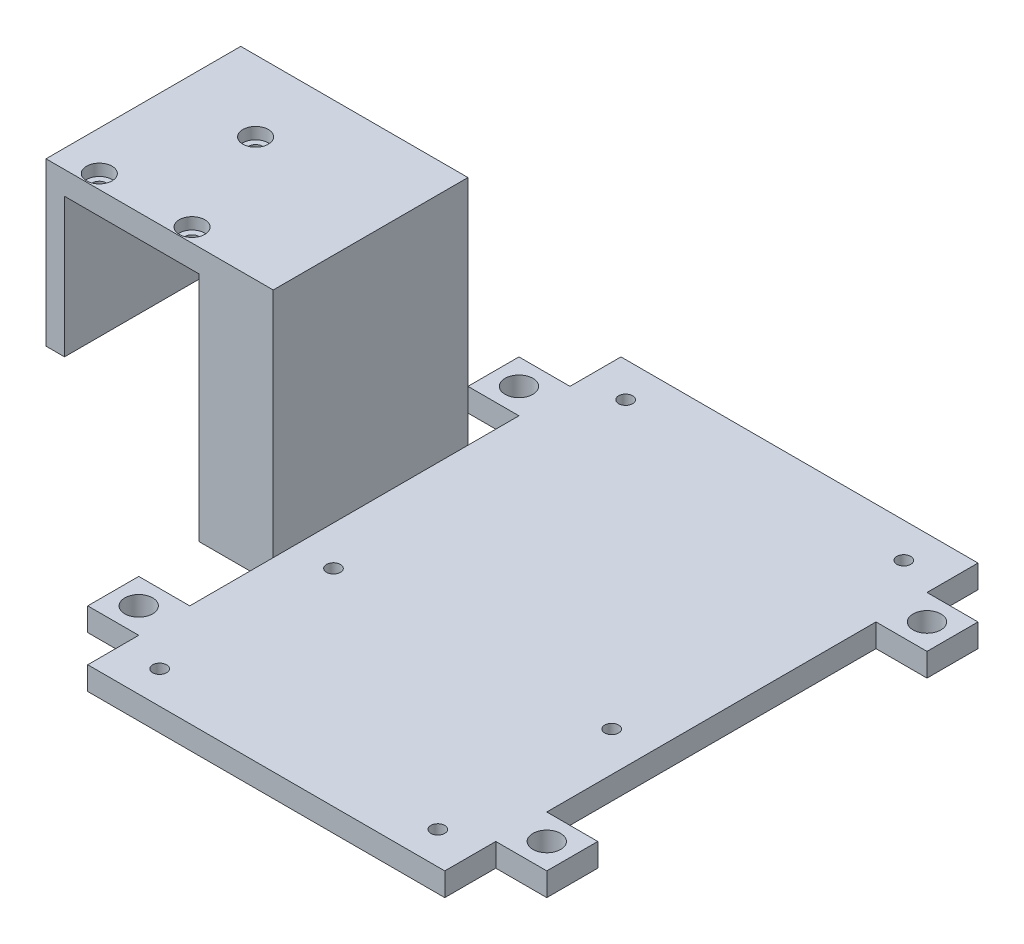
SolidWorks part; units mm, degrees
ref_plane "前视基准面" through (0, 0, 0) normal (0, 0, 1) x (1, 0, 0)
ref_plane "上视基准面" through (0, 0, 0) normal (0, 1, 0) x (1, 0, 0)
ref_plane "右视基准面" through (0, 0, 0) normal (1, 0, 0) x (0, 0, -1)
other "Configuration Table"
sketch "草图1" plane through (0, 0, 0) normal (0, 1, 0) x (1, 0, 0)
  line L1 (-14.5, 42) -> (14.5, 42)
  line L2 (-14.5, 42) -> (-14.5, 0)
  line L3 (-14.5, 0) -> (14.5, 0)
  line L4 (14.5, 42) -> (14.5, 0)
  line L6 (-14.5, 42) -> (-18.5, 42)
  line L7 (-14.5, 42) -> (-14.5, 0)
  line L8 (-14.5, 0) -> (-18.5, 0)
  line L9 (-18.5, 42) -> (-18.5, 0)
  line L10 (14.5, 42) -> (34.5, 42)
  line L11 (14.5, 42) -> (14.5, 0)
  line L12 (14.5, 0) -> (34.5, 0)
  line L13 (34.5, 42) -> (34.5, 0)
  line L14 (30.5, 75) -> (107.5, 75)
  line L15 (30.5, 75) -> (30.5, -40)
  line L16 (30.5, -40) -> (107.5, -40)
  line L17 (107.5, 75) -> (107.5, -40)
  point P4 (0, 0)
  dimension "D1" = 29
  dimension "D2" = 42
  dimension "D3" = 4
  dimension "D4" = 20
  dimension "D5" = 77
  dimension "D6" = 115
  dimension "D7" = 40
  dimension "D8" = 16
extrude "凸台-拉伸2" add sketch "草图1" along normal blind 90 contours L6 L9 L8 L2 | L4 L1 L2 L3 | L15 L10 L4 L12 | L10 L15 L12 L13 | L17 L14 L15 L10 L13 L12 L16 region at (0, 0, -21) region at (-16.5, 0, -21) region at (22.5, 0, -21) region at (69.7059, 0, -17.4323) region at (32.5, 0, -21)
extrude "切除-拉伸3" cut sketch "草图1<6>" against normal blind 1 and the other way blind 30 contours L4 L1 L2 L3 region at (0, 0, -21)
sketch "草图1<6>" plane through (0, 0, 0) normal (0, 1, 0) x (1, 0, 0) same geometry as "草图1"
sketch "草图7" plane through (0, 90, 0) normal (0, 1, 0) x (1, 0, 0)
  line L1 (30.5, 75) -> (107.5, 75)
  line L2 (30.5, 75) -> (30.5, -40)
  line L3 (30.5, -40) -> (107.5, -40)
  line L4 (107.5, 75) -> (107.5, -40)
extrude "切除-拉伸5" cut sketch "草图7" against normal offset from surface (85 mm away) 5 up to face at (45.75, 0, -19.25)
sketch "草图8" plane through (0, 90, 0) normal (0, 1, 0) x (1, 0, 0)
  line L1 (-18.5, 42) -> (30.5, 42)
  line L2 (-18.5, 42) -> (-18.5, 0)
  line L3 (-18.5, 0) -> (30.5, 0)
  line L4 (30.5, 42) -> (30.5, 0)
extrude "切除-拉伸6" cut sketch "草图8" against normal offset from surface (55 mm away) 5 up to face at (0, 30, -21)
sketch "草图9" plane through (0, 30, 0) normal (0, -1, 0) x (1, 0, 0)
  line L0 (0, 27.0422) -> (0, -59.968) construction
  line L2 (-14.5, 0) -> (14.5, 0) construction
  circle A0 centre (-10, -3) radius 1.5
  circle A1 centre (10, -3) radius 1.5
  circle A2 centre (0, -26.7) radius 1.5
  dimension "D1" = 3
  dimension "D3" = 3
  dimension "D5" = 3
  dimension "D2" = 23.7
  dimension "D4" = 20
sketch "草图11" plane through (0, 0, 0) normal (0, -1, 0) x (1, 0, 0)
  line L0 (69, 40) -> (69, -81.7465) construction
  line L1 (30.5, 40) -> (107.5, 40) construction
  circle A0 centre (39, 33) radius 1.5
  circle A1 centre (99, 33) radius 1.5
  circle A2 centre (39, -4.5) radius 1.5
  circle A3 centre (99, -4.5) radius 1.5
  circle A4 centre (99, -67.5) radius 1.5
  circle A5 centre (39, -67.5) radius 1.5
  dimension "D1" = 3
  dimension "D4" = 37.5
  dimension "D5" = 3
  dimension "D7" = 3
  dimension "D9" = 63
  dimension "D2" = 7
  dimension "D3" = 60
extrude "切除-拉伸9" cut sketch "草图11" against normal blind 6
sketch "草图14" plane through (0, 0, 0) normal (0, -1, 0) x (1, 0, 0)
  circle A0 centre (39, 33) radius 3
  circle A1 centre (99, 33) radius 3
  circle A2 centre (39, -4.5) radius 3
  circle A3 centre (99, -4.5) radius 3
  circle A4 centre (39, -67.5) radius 3
  circle A5 centre (99, -67.5) radius 3
  dimension "D1" = 6
extrude "切除-拉伸11" cut sketch "草图14" against normal blind 2
sketch "草图15" plane through (0, 0, 0) normal (0, -1, 0) x (1, 0, 0)
  line L0 (30.5, 40) -> (107.5, 40) construction
  line L1 (69, 40) -> (69, -84.4429) construction
  line L2 (39, -4.5) -> (99, -4.5) construction
  circle A0 centre (39, -4.5) radius 1.5 construction
  circle A1 centre (69, -4.5) radius 2
  ellipse E0 centre (69, -40) end of major axis (69, -37) minor radius 2
  dimension "D3" = 35.5
  dimension "D4" = 4
  dimension "D1" = 4
  dimension "D2" = 6
sketch "草图18" plane through (0, 35, 0) normal (0, 1, 0) x (1, 0, 0)
  line L1 (-18.5, 42) -> (30.5, 42)
  line L2 (-18.5, 42) -> (-18.5, 0)
  line L3 (-18.5, 0) -> (30.5, 0)
  line L4 (30.5, 42) -> (30.5, 0)
extrude "凸台-拉伸3" add sketch "草图18" along normal blind 20
sketch "草图19" plane through (0, 30, 0) normal (0, -1, 0) x (1, 0, 0)
  line L1 (-14.5, 0) -> (14.5, 0)
  line L2 (-14.5, 0) -> (-14.5, -42)
  line L3 (-14.5, -42) -> (14.5, -42)
  line L4 (14.5, 0) -> (14.5, -42)
extrude "切除-拉伸14" cut sketch "草图19" against normal offset from surface (20 mm away) 5 up to face at (6, 55, -21)
sketch "草图20" plane through (0, 50, 0) normal (0, -1, 0) x (1, 0, 0)
  circle A0 centre (-10, -3) radius 1.5
  circle A1 centre (10, -3) radius 1.5
  circle A2 centre (0, -26.7) radius 1.5
extrude "切除-拉伸15" cut sketch "草图20" against normal through all
sketch "草图21" plane through (0, 55, 0) normal (0, 1, 0) x (1, 0, 0)
  circle A0 centre (0, 26.7) radius 2.75
  circle A1 centre (-10, 3) radius 2.75
  circle A2 centre (10, 3) radius 2.75
  dimension "D1" = 5.5
extrude "切除-拉伸16" cut sketch "草图21" against normal offset from surface (2.5 mm away) 2.5 up to face at (-10, 50, -4.5)
sketch "草图22" plane through (0, 0, 0) normal (0, -1, 0) x (1, 0, 0)
  line L1 (30.5, 40) -> (19.5, 40)
  line L2 (30.5, 40) -> (30.5, 29)
  line L3 (30.5, 29) -> (19.5, 29)
  line L4 (19.5, 40) -> (19.5, 29)
  line L5 (107.5, 40) -> (118.5, 40)
  line L6 (107.5, 40) -> (107.5, 29)
  line L7 (107.5, 29) -> (118.5, 29)
  line L8 (118.5, 40) -> (118.5, 29)
  line L9 (30.5, -75) -> (19.5, -75)
  line L10 (30.5, -75) -> (30.5, -64)
  line L11 (30.5, -64) -> (19.5, -64)
  line L12 (19.5, -75) -> (19.5, -64)
  line L13 (107.5, -75) -> (118.5, -75)
  line L14 (107.5, -75) -> (107.5, -64)
  line L15 (107.5, -64) -> (118.5, -64)
  line L16 (118.5, -75) -> (118.5, -64)
  dimension "D1" = 11
  dimension "D2" = 11
  dimension "D3" = 11
  dimension "D4" = 11
  dimension "D5" = 11
  dimension "D6" = 11
  dimension "D7" = 11
  dimension "D8" = 11
sketch "草图25" plane through (0, 0, 0) normal (0, -1, 0) x (1, 0, 0)
  line L1 (-18.5, 0) -> (-14.5, 0)
  line L2 (-18.5, 0) -> (-18.5, -42)
  line L3 (-18.5, -42) -> (-14.5, -42)
  line L4 (-14.5, 0) -> (-14.5, -42)
extrude "切除-拉伸18" cut sketch "草图25" against normal blind 20
sketch "草图26" plane through (0, 0, 0) normal (0, -1, 0) x (1, 0, 0)
  line L6 (30.5, 29) -> (19.5, 29)
  line L7 (30.5, 29) -> (30.5, 18)
  line L8 (30.5, 18) -> (19.5, 18)
  line L9 (19.5, 29) -> (19.5, 18)
  line L10 (107.5, 29) -> (118.5, 29)
  line L11 (107.5, 29) -> (107.5, 18)
  line L12 (107.5, 18) -> (118.5, 18)
  line L13 (118.5, 29) -> (118.5, 18)
  line L14 (30.5, -64) -> (19.5, -64)
  line L15 (30.5, -64) -> (30.5, -53)
  line L16 (30.5, -53) -> (19.5, -53)
  line L17 (19.5, -64) -> (19.5, -53)
  line L18 (107.5, -64) -> (118.5, -64)
  line L19 (107.5, -64) -> (107.5, -53)
  line L20 (107.5, -53) -> (118.5, -53)
  line L21 (118.5, -64) -> (118.5, -53)
  dimension "D1" = 11
  dimension "D2" = 11
  dimension "D3" = 11
  dimension "D4" = 11
  dimension "D5" = 11
  dimension "D6" = 11
  dimension "D7" = 11
  dimension "D8" = 11
extrude "凸台-拉伸4" add sketch "草图26" against normal blind 5
sketch "草图27" plane through (0, 0, 0) normal (0, -1, 0) x (1, 0, 0)
  line L0 (19.5, -53) -> (19.5, -64) construction
  line L1 (30.5, -53) -> (19.5, -53) construction
  line L3 (19.5, 29) -> (19.5, 18) construction
  line L5 (19.5, 18) -> (30.5, 18) construction
  circle A0 centre (25, -58.5) radius 5.5
  circle A1 centre (25, 23.5) radius 5.5
  circle A2 centre (113, 23.5) radius 5.5
  circle A3 centre (113, -58.5) radius 5.5
  dimension "D1" = 11
sketch "草图28" plane through (0, 0, 0) normal (0, -1, 0) x (1, 0, 0)
  circle A0 centre (25, 23.5) radius 3
  circle A1 centre (113, 23.5) radius 3
  circle A2 centre (25, -58.5) radius 3
  circle A4 centre (113, -58.5) radius 3
  dimension "D1" = 6
extrude "切除-拉伸19" cut sketch "草图28" against normal through all
sketch "草图32" plane through (0, 0, 0) normal (0, 0, 1) x (1, 0, 0)
  line L0 (-11.8737, 55) -> (-11.8737, 50) construction
  line L1 (-18.5, 55) -> (30.5, 55) construction
  line L2 (14.5, 50) -> (-14.5, 50) construction
sketch "草图33" plane through (0, 0, 0) normal (0, -1, 0) x (1, 0, 0)
  line L0 (-18.5, -42) -> (123.8425, -42) construction
  line L1 (118.5, -53) -> (118.5, -23.2876) construction
  line L2 (107.5, -75) -> (107.5, -64) construction
  circle A0 centre (39, 33) radius 3 construction
  circle A1 centre (39, 33) radius 1.5 construction
  circle A2 centre (25, 23.5) radius 3 construction
  circle A3 centre (-10, -3) radius 1.5 construction
